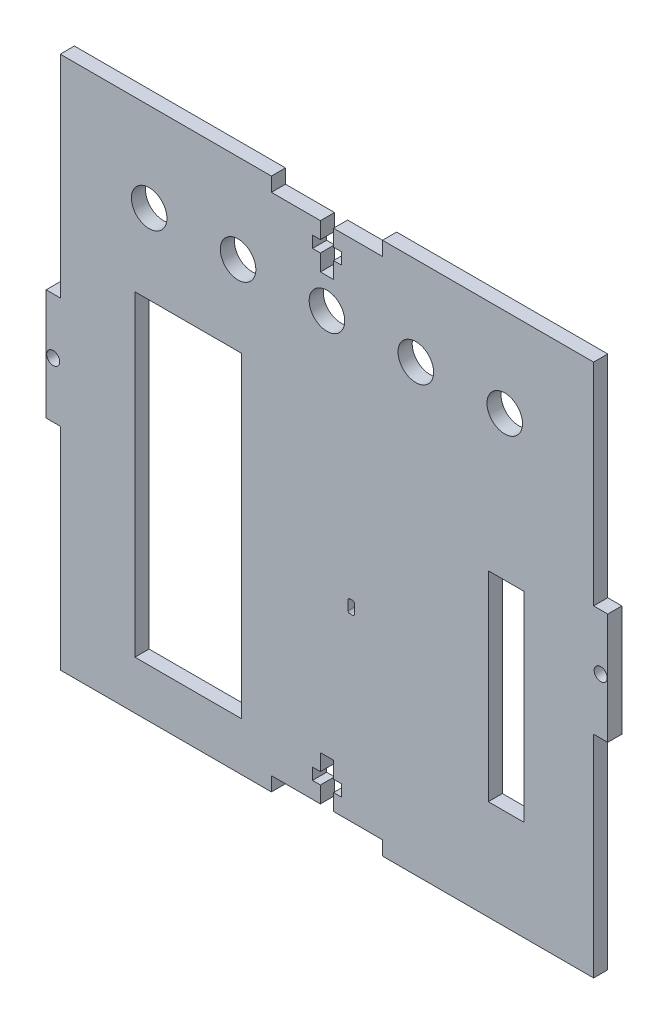
SolidWorks part; units mm, degrees
ref_plane "Front Plane" through (0, 0, 0) normal (0, 0, 1) x (1, 0, 0)
ref_plane "Top Plane" through (0, 0, 0) normal (0, 1, 0) x (1, 0, 0)
ref_plane "Right Plane" through (0, 0, 0) normal (1, 0, 0) x (0, 0, -1)
sketch "Sketch1" plane through (0, 0, 0) normal (0, 0, 1) x (1, 0, 0)
  line L0 (0, 60) -> (0, -60) construction
  line L1 (-60, 60) -> (60, 60)
  line L2 (-60, 60) -> (-60, -60)
  line L3 (-60, -60) -> (60, -60)
  line L4 (60, 60) -> (60, -60)
  line L5 (-60, 60) -> (60, -60) construction
  line L6 (-60, -60) -> (60, 60) construction
  line L7 (-60, 0) -> (60, 0) construction
  line L8 (-3.25, -50.525) -> (3.25, -50.525)
  line L9 (12.5, 60) -> (-12.5, 60)
  line L10 (12.5, 60) -> (12.5, 56.825)
  line L11 (12.5, 56.825) -> (-12.5, 56.825)
  line L12 (-12.5, 60) -> (-12.5, 56.825)
  line L13 (12.5, 60) -> (-12.5, 56.825) construction
  line L14 (12.5, 56.825) -> (-12.5, 60) construction
  line L15 (-1.47, 56.825) -> (1.47, 56.825)
  line L16 (-1.47, 56.825) -> (-1.47, 46.825)
  line L17 (-1.47, 46.825) -> (1.47, 46.825)
  line L18 (1.47, 56.825) -> (1.47, 46.825)
  line L19 (-1.47, 56.825) -> (1.47, 46.825) construction
  line L20 (-1.47, 46.825) -> (1.47, 56.825) construction
  line L21 (-3.25, 53.125) -> (3.25, 53.125)
  line L22 (-3.25, 53.125) -> (-3.25, 50.525)
  line L23 (-3.25, 50.525) -> (3.25, 50.525)
  line L24 (3.25, 53.125) -> (3.25, 50.525)
  line L25 (-3.25, 53.125) -> (3.25, 50.525) construction
  line L26 (-3.25, 50.525) -> (3.25, 53.125) construction
  line L27 (3.25, -53.125) -> (3.25, -50.525)
  line L28 (-3.25, -53.125) -> (3.25, -53.125)
  line L29 (-3.25, -53.125) -> (-3.25, -50.525)
  line L30 (-1.47, -46.825) -> (1.47, -46.825)
  line L31 (1.47, -56.825) -> (1.47, -46.825)
  line L32 (-1.47, -56.825) -> (1.47, -56.825)
  line L33 (-1.47, -56.825) -> (-1.47, -46.825)
  line L34 (12.5, -56.825) -> (-12.5, -56.825)
  line L35 (-12.5, -60) -> (-12.5, -56.825)
  line L36 (12.5, -60) -> (-12.5, -60)
  line L37 (12.5, -60) -> (12.5, -56.825)
  line L38 (63.175, -12.5) -> (60, -12.5)
  line L39 (-63.175, 12.5) -> (-60, 12.5)
  line L40 (-63.175, 12.5) -> (-63.175, -12.5)
  line L41 (-63.175, -12.5) -> (-60, -12.5)
  line L42 (-60, 12.5) -> (-60, -12.5)
  line L43 (-63.175, 12.5) -> (-60, -12.5) construction
  line L44 (-63.175, -12.5) -> (-60, 12.5) construction
  line L45 (60, 12.5) -> (60, -12.5)
  line L46 (63.175, 12.5) -> (60, 12.5)
  line L47 (63.175, 12.5) -> (63.175, -12.5)
  circle A0 centre (-61.5875, 0) radius 1.47
  circle A1 centre (61.5875, 0) radius 1.47
  point P0 (0, 0)
  point P10 (0, 58.4125)
  point P15 (0, 51.825)
  point P20 (0, 51.825)
  point P37 (-61.5875, 0)
  dimension "D11" = 2.94
  dimension "D1" = 120
  dimension "D2" = 120
  dimension "D3" = 3.175
  dimension "D4" = 10
  dimension "D5" = 2.94
  dimension "D6" = 25
  dimension "D7" = 6.5
  dimension "D8" = 2.6
  dimension "D9" = 6.3
  dimension "D10" = 3.175
extrude "Boss-Extrude1" add sketch "Sketch1" along normal mid plane 3.175 contours L21 L24 L23 L18 L17 L16 L22 L11 L12 L1 L2 L3 L4 L10 | L40 L39 L42 L41 | A0 | L38 L45 L46 L47 | A1 region at (0, 0, 0)
sketch "Sketch3" plane through (0, 0, -1.5875) normal (0, 0, -1) x (-1, 0, 0)
  line L0 (-9.6476, 0) -> (-9.6476, -15) construction
  line L5 (-9.6476, -15) -> (-19.2951, -15) construction
  line L6 (-40.3, 7.5) -> (-40.3, -22.5) construction
  line L7 (-36.3, 7.5) -> (-44.3, 7.5)
  line L8 (-36.3, 7.5) -> (-36.3, -37.5)
  line L9 (-36.3, -37.5) -> (-44.3, -37.5)
  line L10 (-44.3, 7.5) -> (-44.3, -37.5)
  line L11 (-38.7125, -40) -> (-38.7125, 10) construction
  line L12 (-41.8875, 10) -> (-41.8875, -40) construction
  line L13 (0, 0) -> (-19.2951, 0) construction
  dimension "D1" = 8
  dimension "D2" = 45
  dimension "D3" = 15
extrude "Cut-Extrude1" cut sketch "Sketch3" against normal through all
sketch "Sketch4" plane through (0, 0, -1.5875) normal (0, 0, -1) x (-1, 0, 0)
  line L0 (43.2, 21.2555) -> (43.2, -48.2445) construction
  line L1 (43.2, 22.1055) -> (19.2, 22.1055)
  line L2 (43.2, 22.1055) -> (43.2, -49.0945)
  line L3 (43.2, -49.0945) -> (19.2, -49.0945)
  line L4 (19.2, 22.1055) -> (19.2, -49.0945)
  line L5 (19.2, -48.2445) -> (19.2, 21.2555) construction
  line L6 (20.05, 22.1055) -> (26.7, 22.1055) construction
  line L7 (42.35, -49.0945) -> (20.05, -49.0945) construction
extrude "Cut-Extrude2" cut sketch "Sketch4" against normal through all
sketch "Sketch5" plane through (0, 0, -1.5875) normal (0, 0, -1) x (-1, 0, 0)
  line L0 (-5.1534, -16.25) -> (-5.7792, -16.25) construction
  line L1 (-5.7792, -13.75) -> (-5.1534, -13.75) construction
  line L2 (-4.9534, -13.95) -> (-4.9534, -16.05) construction
  line L3 (-5.1534, -16.25) -> (-5.7792, -16.25)
  line L4 (-5.7792, -13.75) -> (-5.1534, -13.75)
  line L5 (-4.9534, -13.95) -> (-4.9534, -16.05)
  line L6 (-5.1534, -16.45) -> (-5.7792, -16.45)
  line L7 (-5.7792, -13.55) -> (-5.1534, -13.55)
  line L8 (-4.7534, -13.95) -> (-4.7534, -16.05)
  arc A0 (-5.1534, -16.25) -> (-4.9534, -16.05) centre (-5.1534, -16.05) ccw construction
  arc A1 (-5.9775, -16.0753) -> (-5.7792, -16.25) centre (-5.7792, -16.05) ccw construction
  arc A2 (-5.9775, -13.9247) -> (-5.9775, -16.0753) centre (2.4542, -15) ccw construction
  arc A3 (-5.7792, -13.75) -> (-5.9775, -13.9247) centre (-5.7792, -13.95) ccw construction
  arc A4 (-4.9534, -13.95) -> (-5.1534, -13.75) centre (-5.1534, -13.95) ccw construction
  arc A5 (-5.1534, -16.25) -> (-4.9534, -16.05) centre (-5.1534, -16.05) ccw
  arc A6 (-5.9775, -16.0753) -> (-5.7792, -16.25) centre (-5.7792, -16.05) ccw
  arc A7 (-5.9775, -13.9247) -> (-5.9775, -16.0753) centre (2.4542, -15) ccw
  arc A8 (-5.7792, -13.75) -> (-5.9775, -13.9247) centre (-5.7792, -13.95) ccw
  arc A9 (-4.9534, -13.95) -> (-5.1534, -13.75) centre (-5.1534, -13.95) ccw
  arc A10 (-6.1759, -16.1006) -> (-5.7792, -16.45) centre (-5.7792, -16.05) ccw
  arc A11 (-6.1759, -13.8994) -> (-6.1759, -16.1006) centre (2.4542, -15) ccw
  arc A12 (-5.7792, -13.55) -> (-6.1759, -13.8994) centre (-5.7792, -13.95) ccw
  arc A13 (-4.7534, -13.95) -> (-5.1534, -13.55) centre (-5.1534, -13.95) ccw
  arc A14 (-5.1534, -16.45) -> (-4.7534, -16.05) centre (-5.1534, -16.05) ccw
  dimension "D1" = 0.2
extrude "Cut-Extrude4" cut sketch "Sketch5" against normal through all contours L8 A14 L6 A10 A11 A12 L7 A13
sketch "Sketch6" plane through (0, 0, -1.5875) normal (0, 0, -1) x (-1, 0, 0)
  line L0 (-60, 40) -> (60, 40) construction
  line L1 (-60, 60) -> (-60, 12.5) construction
  line L2 (60, 60) -> (60, 12.5) construction
  line L3 (60, 60) -> (12.5, 60) construction
  line L4 (-40, 40) -> (-20, 40)
  line L5 (-20, 40) -> (0, 40)
  line L6 (0, 40) -> (20, 40)
  line L7 (20, 40) -> (40, 40)
  line L8 (-60, 60) -> (-60, 12.5) construction
  line L9 (0, 40) -> (20, 40)
  line L10 (-20, 40) -> (0, 40)
  line L11 (-40, 40) -> (-20, 40)
  line L12 (-60, 40) -> (-40, 40)
  circle A0 centre (40, 40) radius 4
  circle A1 centre (20, 40) radius 4
  circle A2 centre (0, 40) radius 4
  circle A3 centre (-20, 40) radius 4
  circle A4 centre (-40, 40) radius 4
  dimension "D4" = 8
  dimension "D1" = 20
  dimension "D2" = 20
  dimension "D3" = 20
  dimension "D5" = 5
extrude "Cut-Extrude5" cut sketch "Sketch6" against normal through all contours A0 | A1 | A2 | A3 | A4
